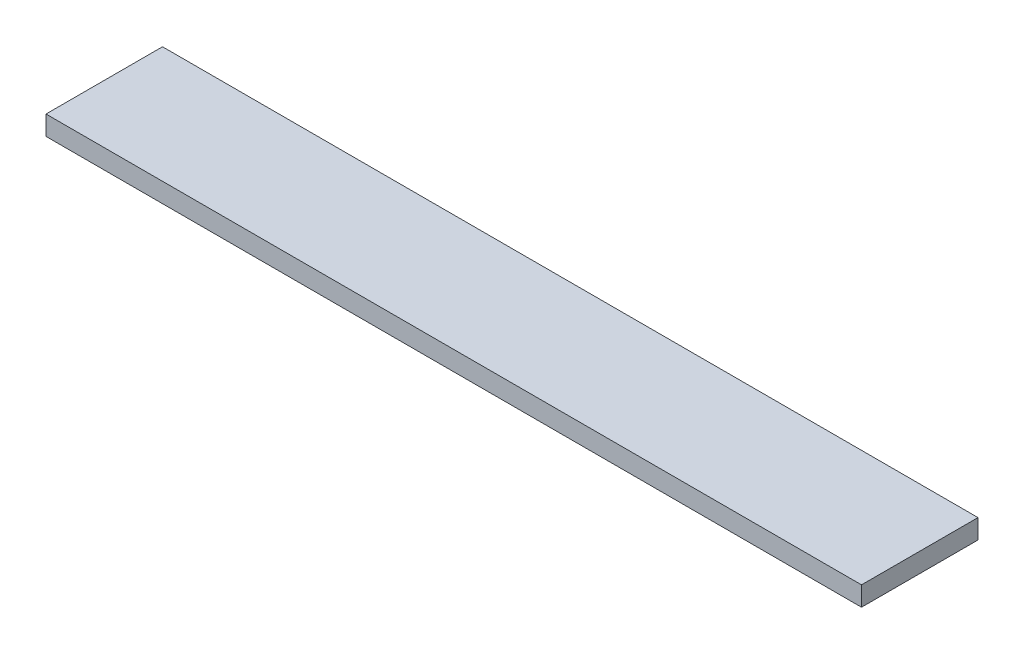
SolidWorks part; units mm, degrees
ref_plane "Front Plane" through (0, 0, 0) normal (0, 0, 1) x (1, 0, 0)
ref_plane "Top Plane" through (0, 0, 0) normal (0, 1, 0) x (1, 0, 0)
ref_plane "Right Plane" through (0, 0, 0) normal (1, 0, 0) x (0, 0, -1)
sketch "Sketch1" plane through (0, 0, 0) normal (0, 1, 0) x (1, 0, 0)
  line L1 (-62.1655, 41.0362) -> (471.2345, 41.0362)
  line L2 (-62.1655, 41.0362) -> (-62.1655, -35.1638)
  line L3 (-62.1655, -35.1638) -> (471.2345, -35.1638)
  line L4 (471.2345, 41.0362) -> (471.2345, -35.1638)
  dimension "D1" = 533.4
  dimension "D2" = 76.2
extrude "Boss-Extrude1" add sketch "Sketch1" along normal blind 12.7
